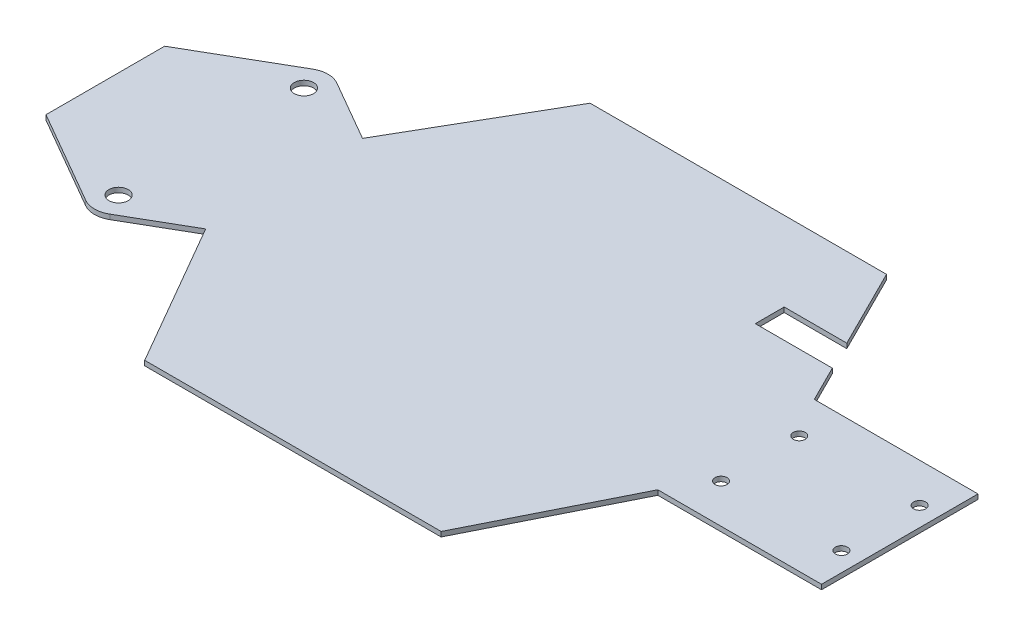
SolidWorks part; units mm, degrees
ref_plane "Front Plane" through (0, 0, 0) normal (0, 0, 1) x (1, 0, 0)
ref_plane "Top Plane" through (0, 0, 0) normal (0, 1, 0) x (1, 0, 0)
ref_plane "Right Plane" through (0, 0, 0) normal (1, 0, 0) x (0, 0, -1)
sketch "Sketch1" plane through (0, 0, 0) normal (0, 1, 0) x (1, 0, 0)
  line L0 (165, 32.5) -> (97, 32.5)
  line L1 (-89.8231, -92.5) -> (67, -92.5)
  line L3 (-56.1347, 92.5) -> (67, 92.5)
  line L4 (165, -32.5) -> (165, 32.5)
  line L5 (-165, -92.5) -> (165, 92.5) construction
  line L6 (-165, 92.5) -> (165, -92.5) construction
  line L7 (97, 32.5) -> (89.5, 47.5)
  line L8 (-187.8754, 0) -> (194.9929, 0) construction
  line L9 (165, -32.5) -> (97, -32.5)
  line L10 (97, -32.5) -> (67, -92.5)
  line L11 (165, 92.5) -> (165, 32.5) construction
  line L12 (67, 92.5) -> (165, 92.5) construction
  line L13 (67, -92.5) -> (165, -92.5) construction
  line L14 (165, -32.5) -> (165, -92.5) construction
  line L16 (107, -16.25) -> (157, -16.25) construction
  line L17 (107, -16.25) -> (107, 16.25) construction
  line L18 (107, 16.25) -> (157, 16.25) construction
  line L19 (157, -16.25) -> (157, 16.25) construction
  line L20 (107, -16.25) -> (157, 16.25) construction
  line L21 (107, 16.25) -> (157, -16.25) construction
  line L25 (-121, -38.5) -> (-89.8231, -92.5) construction
  line L26 (-56.1347, -92.5) -> (-90.7337, -32.5728)
  line L27 (-90.7337, -32.5728) -> (-116, -47.1603)
  line L28 (-121, 38.5) -> (-121, -38.5) construction
  line L29 (-126, -47.1603) -> (-165, -24.6436)
  line L30 (-90.7337, 32.5728) -> (-116, 47.1603)
  line L31 (-56.1347, 92.5) -> (-90.7337, 32.5728)
  line L32 (-165, -24.6436) -> (-165, 24.6436)
  line L33 (-89.8231, -92.5) -> (-165, -92.5) construction
  line L34 (-165, -92.5) -> (-165, 92.5) construction
  line L35 (-165, 92.5) -> (-56.1347, 92.5) construction
  line L36 (-165, 24.6436) -> (-126, 47.1603)
  line L37 (57.5, 47.5) -> (57.5, 59.5)
  line L38 (57.5, 59.5) -> (83.5, 59.5)
  line L39 (57.5, 47.5) -> (89.5, 47.5)
  line L40 (83.5, 59.5) -> (67, 92.5)
  circle A0 centre (-121, 38.5) radius 4
  circle A1 centre (-121, -38.5) radius 4
  circle A2 centre (107, 16.25) radius 2.5
  circle A3 centre (157, 16.25) radius 2.5
  circle A4 centre (107, -16.25) radius 2.5
  circle A5 centre (157, -16.25) radius 2.5
  arc A6 (-126, -47.1603) -> (-116, -47.1603) centre (-121, -38.5) ccw
  arc A7 (-126, 47.1603) -> (-116, 47.1603) centre (-121, 38.5) cw
  point P0 (0, 0)
  point P18 (132, 0)
  point P28 (0, 0)
  point P30 (0, 0)
  dimension "D5" = 8
  dimension "D12" = 5
  dimension "D13" = 5
  dimension "D14" = 5
  dimension "D15" = 5
  dimension "D21" = 10
  dimension "D2" = 185
  dimension "D3" = 65
  dimension "D4" = 30
  dimension "D6" = 330
  dimension "D7" = 54
  dimension "D8" = 68
  dimension "D9" = 32.5
  dimension "D10" = 50
  dimension "D11" = 8
  dimension "D16" = 15
  dimension "D19" = 60
  dimension "D20" = 29.175
  dimension "D22" = 44
  dimension "D23" = 60
  dimension "D24" = 60
  dimension "D25" = 32
  dimension "D27" = 12
extrude "Boss-Extrude1" add sketch "Sketch1" along normal blind 2 contours A7 A6 L27 L26 L1 L10 L9 L4 L0 L7 L3 L31 L30 A5 A4 A3 A2 A0 A1 region at (-1.3739, 0, 0.4576)
